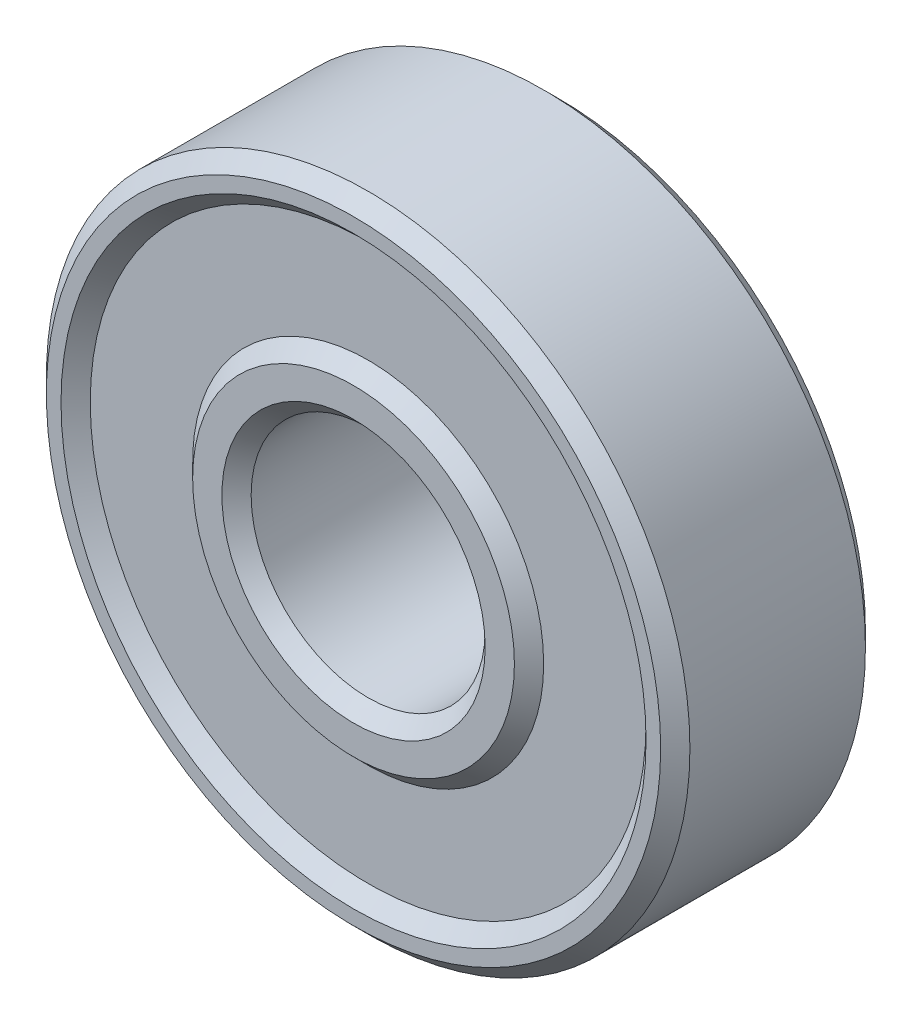
SolidWorks part; units mm, degrees
ref_plane "Plan1" through (0, 0, 0) normal (0, 0, 1) x (1, 0, 0)
ref_plane "Plan2" through (0, 0, 0) normal (0, 1, 0) x (1, 0, 0)
ref_plane "Plan3" through (0, 0, 0) normal (1, 0, 0) x (0, 0, -1)
sketch "Esquisse1" plane through (0, 0, 0) normal (0, 0, 1) x (1, 0, 0)
  circle A0 centre (0, 0) radius 11
  circle A1 centre (0, 0) radius 4
  dimension "D1" = 8
  dimension "D2" = 22
extrude "Base-Extrusion" add sketch "Esquisse1" along normal blind 7
sketch "Esquisse2" plane through (0, 0, 7) normal (0, 0, 1) x (1, 0, 0)
  circle A0 centre (0, 0) radius 9.5
  circle A1 centre (0, 0) radius 6
  dimension "D1" = 12
  dimension "D2" = 19
extrude "Enlèv. mat.-Extru.1" cut sketch "Esquisse2" against normal blind 0.5
sketch "Esquisse3" plane through (0, 0, 0) normal (0, 0, -1) x (-1, 0, 0)
  circle A0 centre (0, 0) radius 9.5
  circle A1 centre (0, 0) radius 6
  dimension "D1" = 12
  dimension "D2" = 19
extrude "Enlèv. mat.-Extru.2" cut sketch "Esquisse3" against normal blind 0.5
chamfer "Chanfrein1" distance 0.5 angle 45 8 edges at (9.5, 0, 7) (6, 0, 7) (-9.5, 0, 0) (-6, 0, 0) (11, 0, 0) (11, 0, 7) (4, 0, 0) (4, 0, 7)
